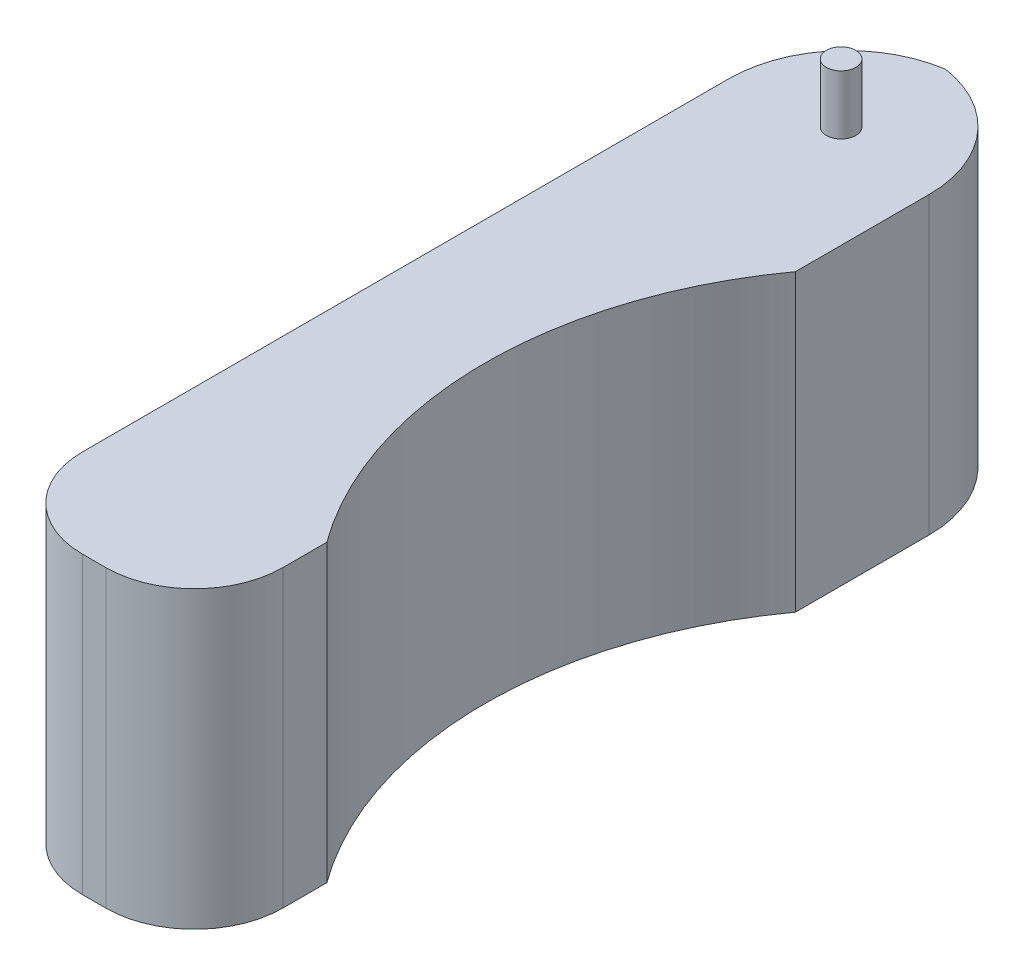
SolidWorks part; units mm, degrees
ref_plane "Спереди" through (0, 0, 0) normal (0, 0, 1) x (1, 0, 0)
ref_plane "Сверху" through (0, 0, 0) normal (0, 1, 0) x (1, 0, 0)
ref_plane "Справа" through (0, 0, 0) normal (1, 0, 0) x (0, 0, -1)
sketch "Эскиз2" plane through (0, 0, 0) normal (0, 1, 0) x (1, 0, 0)
  line L0 (20.7753, -61.7645) -> (20.7753, -69.2243)
  line L1 (-13.1951, 60.3607) -> (20.7753, 60.3607)
  line L2 (-13.1951, 60.3607) -> (-13.1951, -69.2243)
  line L3 (1.8049, -84.2243) -> (5.7753, -84.2243)
  line L4 (20.7753, 60.3607) -> (20.7753, 17.6871)
  arc A0 (20.7753, 17.6871) -> (20.7753, -61.7645) centre (75.4324, -22.0387) ccw
  arc A1 (-13.1951, -69.2243) -> (1.8049, -84.2243) centre (1.8049, -69.2243) ccw
  arc A2 (5.7753, -84.2243) -> (20.7753, -69.2243) centre (5.7753, -69.2243) ccw
  dimension "D1" = 15
extrude "Бобышка-Вытянуть1" add sketch "Эскиз2" along normal blind 50 contours L4 A0 L0 A2 L3 A1 L2 L1
sketch "Эскиз3" plane through (0, 50, 0) normal (0, 1, 0) x (1, 0, 0)
  circle A0 centre (3.4031, 42.8007) radius 2.5
extrude "Бобышка-Вытянуть2" add sketch "Эскиз3" along normal blind 10 contours A0
fillet "Скругление1" radius 20 2 edges at (-13.1951, 25, -60.3607) (20.7753, 25, -60.3607)
